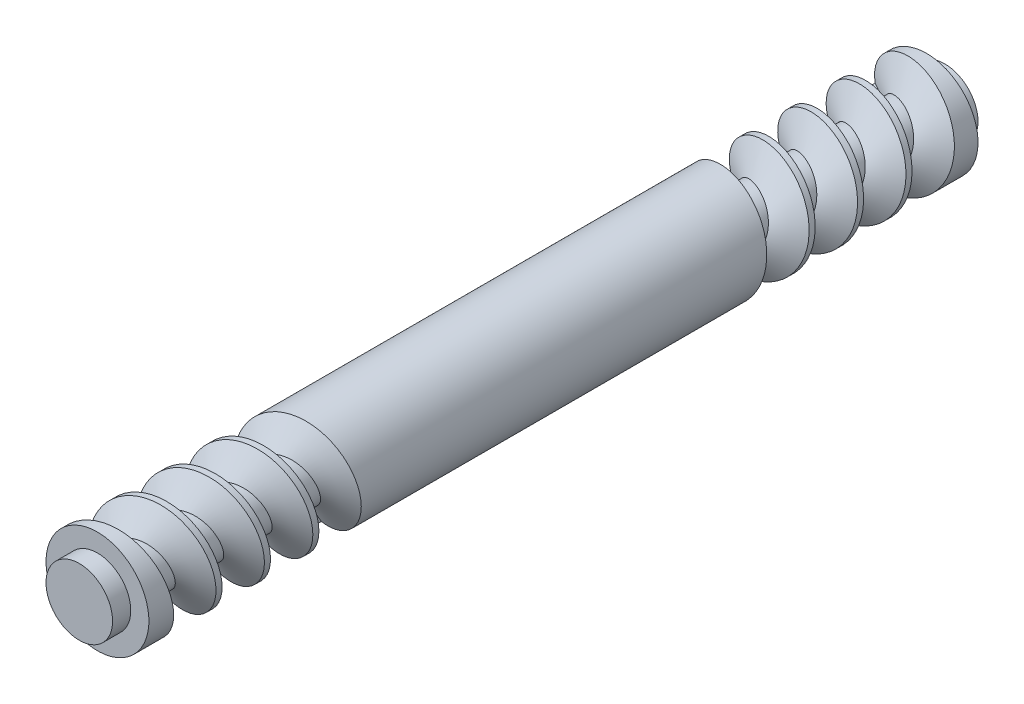
SolidWorks part; units mm, degrees
ref_plane "Plan de face" through (0, 0, 0) normal (0, 0, 1) x (1, 0, 0)
ref_plane "Plan de dessus" through (0, 0, 0) normal (0, 1, 0) x (1, 0, 0)
ref_plane "Plan de droite" through (0, 0, 0) normal (1, 0, 0) x (0, 0, -1)
sketch "Esquisse1" plane through (0, 0, 0) normal (0, 0, 1) x (1, 0, 0)
  circle A0 centre (0, 0) radius 4.25
  dimension "D1" = 8.5
extrude "Boss.-Extru.1" add sketch "Esquisse1" along normal mid plane 68.5
sketch "Esquisse3" plane through (0, 0, 34.25) normal (0, 0, 1) x (1, 0, 0)
  circle A0 centre (0, 0) radius 2.75
  dimension "D1" = 5.5
extrude "Boss.-Extru.2" add sketch "Esquisse3" along normal blind 1.5
mirror "Symétrie1" about plane through (0, 0, 0) normal (0, 0, 1) of "Boss.-Extru.2"
thread "Filetage1" pitch 4 method cut profile "Profil de filetage1" start angle 0, offset 0, length 15, pitch 4, diameter 8.5
ref_plane "Plan1" through (-4.25, 0, 34.25) normal (0, -1, 0) x (-1, 0, 0)
sketch "Profil de filetage1" plane through (-4.25, 0, 34.25) normal (0, -1, 0) x (-1, 0, 0)
  line L0 (0, 0) -> (0, 4) construction
  line L11 (0, 0) -> (0, 3.5)
  line L12 (0, 3.5) -> (-2.1651, 2.25)
  line L13 (-2.1651, 2.25) -> (-2.1651, 1.25)
  line L15 (-2.1651, 1.25) -> (0, 0)
  line L17 (-2.1651, 1.75) -> (0, 1.75) construction
  point P2 (0, 0)
  dimension "Pitch" = 4
  dimension "Profile_Angle" = 60
  dimension "Profile_Land" = 1
  dimension "Profile_Height" = 2.1651
mirror "Symétrie4" about plane through (0, 0, 0) normal (0, 0, 1) of "Filetage1"
